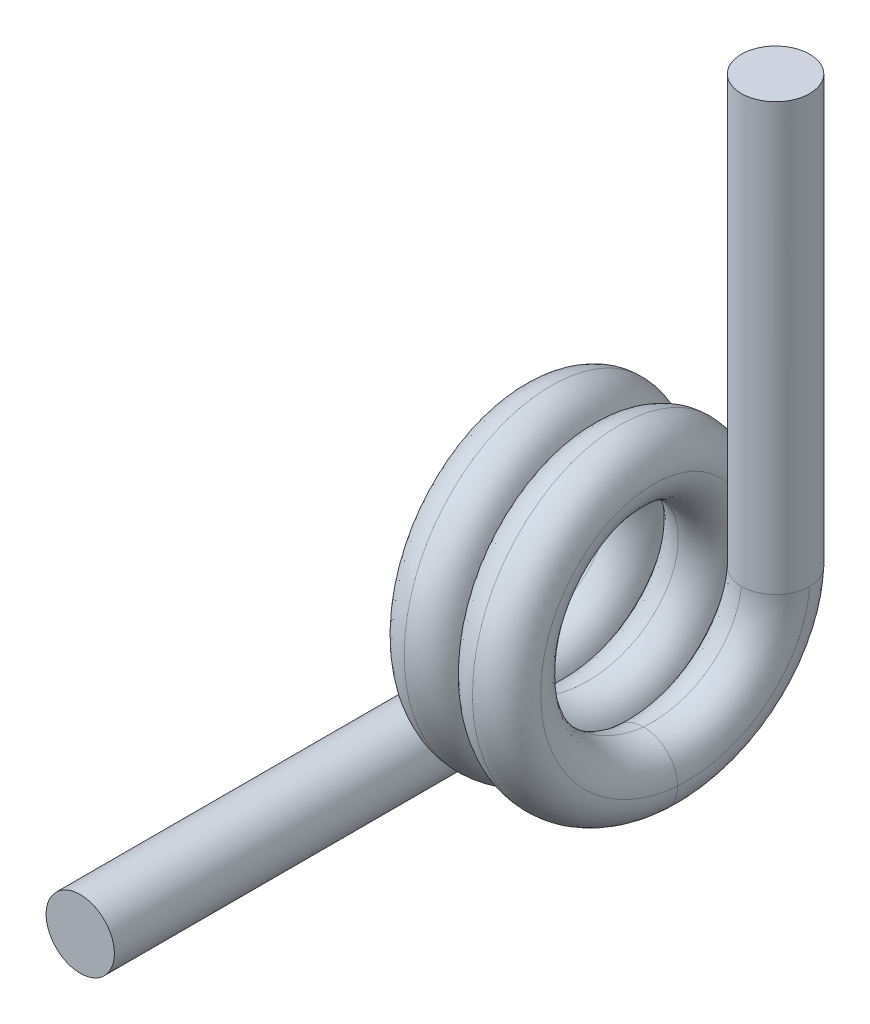
SolidWorks part; units mm, degrees
note: '?' marks a value the reader was unsure of.
ref_plane "Front Plane" through (0, 0, 0) normal (0, 0, 1) x (1, 0, 0)
ref_plane "Top Plane" through (0, 0, 0) normal (0, 1, 0) x (1, 0, 0)
ref_plane "Right Plane" through (0, 0, 0) normal (1, 0, 0) x (0, 0, -1)
sketch3d "Origin Point"
  point P0 (0, 0, 0)
sketch "Sketch1" plane through (0, 0, 0) normal (0, 0, 1) x (1, 0, 0)
  circle A0 centre (0, 0) radius 0.5207
  dimension "D1" = 1.0414
sketch "Helix Reference" plane through (0, 0, 0) normal (1, 0, 0) x (0, 0, -1)
  line L0 (0, -0.5207) -> (2.3432, -0.5207) construction
  line L1 (2.3432, -0.5207) -> (2.3432, 1.8225) construction
  line L2 (0, 0.5207) -> (0, -0.5207) construction
  dimension "D1" = 2.3432
sketch "Sketch3" plane through (0, 0, 0) normal (1, 0, 0) x (0, 0, -1)
  circle A0 centre (2.3432, 1.8225) radius 2.3432
curve "Main Helix" pitch 1.0414 height 2.0828 turns 2
ref_plane "Helix Center Plane" through (0, 0, -2.3432) normal (0, 0, 1) x (1, 0, 0)
sketch "Secondary Helix Reference" plane through (0, 0, -2.3432) normal (0, 0, 1) x (1, 0, 0)
  line L0 (0, 0) -> (2.0828, 0) construction
  line L1 (2.0828, 0) -> (2.0828, -0.5207) construction
ref_plane "Helix End Plane" through (2.0828, 0, 0) normal (1, 0, 0) x (0, 0, -1)
sketch "Sketch9" plane through (2.0828, 0, 0) normal (1, 0, 0) x (0, 0, -1)
  circle A0 centre (2.3432, 1.8225) radius 2.3432 construction
  circle A1 centre (2.3432, 1.8225) radius 2.3432
curve "Secondary Helix" pitch 0.762 height 0.1905 turns 0.25
extrude "Horizontal Extension" add sketch "Sketch1" against normal up to vertex (2.3432 mm away) contours A0 up to point (0, -0.5207, -2.3432)
sketch "Sketch4" plane through (0, 0, -2.3432) normal (0, 0, -1) x (-1, 0, 0)
  circle A1 centre (0, 0) radius 0.5207
  circle A2 centre (0, 0) radius 0.5207
  dimension "D1" = 0
sweep "Main Helix Sweep" add profiles "Sketch4" path "Main Helix"
sketch "Sketch5" plane through (0, 0, -2.3432) normal (0, 0, -1) x (-1, 0, 0)
  arc A4 (-2.6035, 0) -> (-2.0828, -0.5207) centre (-2.0828, 0) ccw
  arc A5 (-2.0828, -0.5207) -> (-1.5621, 0) centre (-2.0828, 0) ccw
  arc A6 (-1.5621, 0) -> (-2.0828, 0.5207) centre (-2.0828, 0) ccw
  arc A7 (-2.0828, 0.5207) -> (-2.6035, 0) centre (-2.0828, 0) ccw
  arc A8 (-2.6035, 0) -> (-2.0828, -0.5207) centre (-2.0828, 0) ccw
  arc A9 (-2.0828, -0.5207) -> (-1.5621, 0) centre (-2.0828, 0) ccw
  arc A10 (-1.5621, 0) -> (-2.0828, 0.5207) centre (-2.0828, 0) ccw
  arc A11 (-2.0828, 0.5207) -> (-2.6035, 0) centre (-2.0828, 0) ccw
  dimension "D1" = 0
ref_plane "Helix End Plane, Secondary" through (2.0828, 0, 0) normal (1, 0, 0) x (0, 0, -1)
sweep "Secondary Helix Sweep" add profiles "Sketch5" path "Secondary Helix"
sketch "Sketch10" plane through (0, 1.8224, 0) normal (0, 1, 0) x (1, 0, 0)
  arc A4 (2.2733, 4.6863) -> (1.7526, 4.1656) centre (2.2733, 4.1656) ccw
  arc A5 (1.7526, 4.1656) -> (2.2733, 3.6449) centre (2.2733, 4.1656) ccw
  arc A6 (2.2733, 3.6449) -> (2.794, 4.1656) centre (2.2733, 4.1656) ccw
  arc A7 (2.794, 4.1656) -> (2.2733, 4.6863) centre (2.2733, 4.1656) ccw
  arc A8 (2.2733, 4.6863) -> (1.7526, 4.1656) centre (2.2733, 4.1656) ccw
  arc A9 (1.7526, 4.1656) -> (2.2733, 3.6449) centre (2.2733, 4.1656) ccw
  arc A10 (2.2733, 3.6449) -> (2.794, 4.1656) centre (2.2733, 4.1656) ccw
  arc A11 (2.794, 4.1656) -> (2.2733, 4.6863) centre (2.2733, 4.1656) ccw
  dimension "D1" = 0
sketch "Helix Top Point" plane through (0, 0, -2.3432) normal (0, 0, 1) x (1, 0, 0)
  point P0 (1.5621, 4.1656)
extrude "Vertical Extension" add sketch "Sketch10" along normal up to vertex (2.3432 mm away) separate body contours A11 A8 A9 A10 up to point (1.5621, 4.1656, -2.3432)
combine bodies "Combine" operation type add bodies to combine 102 103 104
sketch "Sketch12" plane through (0, 4.1656, 0) normal (0, 1, 0) x (1, 0, 0)
  circle A1 centre (2.2733, 4.1656) radius 0.5207
  circle A2 centre (2.2733, 4.1656) radius 0.5207
  dimension "D1" = 0
extrude "Vertical Arm" add sketch "Sketch12" along normal blind 4.1656
sketch "Sketch13" plane through (0, 0, 0) normal (0, 0, 1) x (1, 0, 0)
  circle A1 centre (0, 0) radius 0.5207
  circle A2 centre (0, 0) radius 0.5207
  dimension "D1" = 0
extrude "Horizontal Arm" add sketch "Sketch13" along normal blind 4.1656
ref_axis "Helix Centerline" through (0, 1.8225, -2.3432) along (1, 0, 0)?
